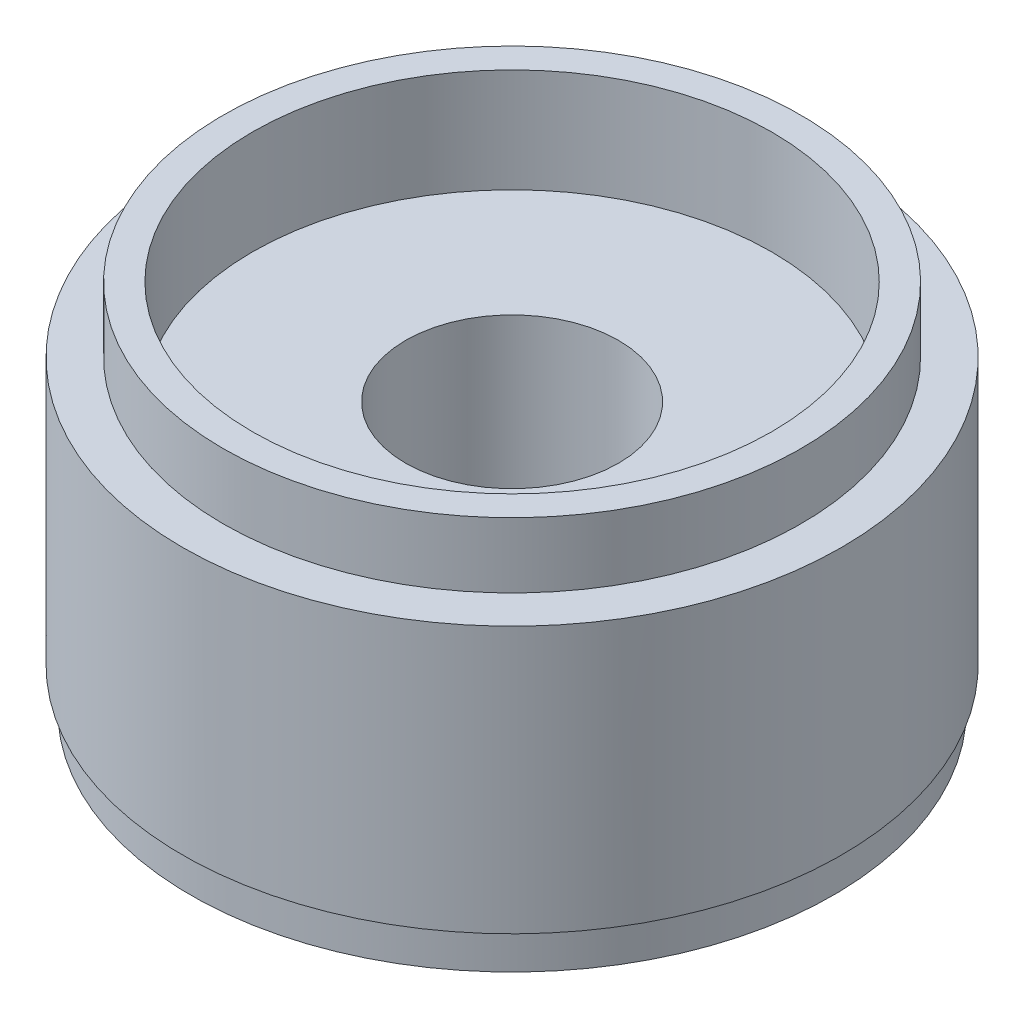
SolidWorks part; units mm, degrees
ref_plane "Front Plane" through (0, 0, 0) normal (0, 0, 1) x (1, 0, 0)
ref_plane "Top Plane" through (0, 0, 0) normal (0, 1, 0) x (1, 0, 0)
ref_plane "Right Plane" through (0, 0, 0) normal (1, 0, 0) x (0, 0, -1)
sketch "Sketch1" plane through (0, 0, 0) normal (0, 1, 0) x (1, 0, 0)
  circle A0 centre (0, 0) radius 25.385
extrude "Boss-Extrude1" add sketch "Sketch1" along normal blind 28.54 separate body
sketch "Sketch2" plane through (0, 0, 0) normal (0, -1, 0) x (1, 0, 0)
  circle A0 centre (0, 0) radius 24.75
extrude "Cut-Extrude1" cut sketch "Sketch2" against normal blind 3 flip side to cut
sketch "Sketch3" plane through (0, 28.54, 0) normal (0, 1, 0) x (1, 0, 0)
  circle A0 centre (0, 0) radius 22.25
extrude "Cut-Extrude2" cut sketch "Sketch3" against normal blind 5.02 flip side to cut
sketch "Sketch4" plane through (0, 28.54, 0) normal (0, 1, 0) x (1, 0, 0)
  circle A0 centre (0, 0) radius 20
extrude "Cut-Extrude3" cut sketch "Sketch4" against normal blind 8
sketch "Sketch5" plane through (0, 0, 0) normal (0, -1, 0) x (1, 0, 0)
  circle A0 centre (0, 0) radius 8.2
extrude "Cut-Extrude4" cut sketch "Sketch5" against normal through all
sketch "Sketch6" plane through (0, 0, 0) normal (0, -1, 0) x (1, 0, 0)
  circle A0 centre (0, 0) radius 13.5
extrude "Cut-Extrude5" cut sketch "Sketch6" against normal blind 5
